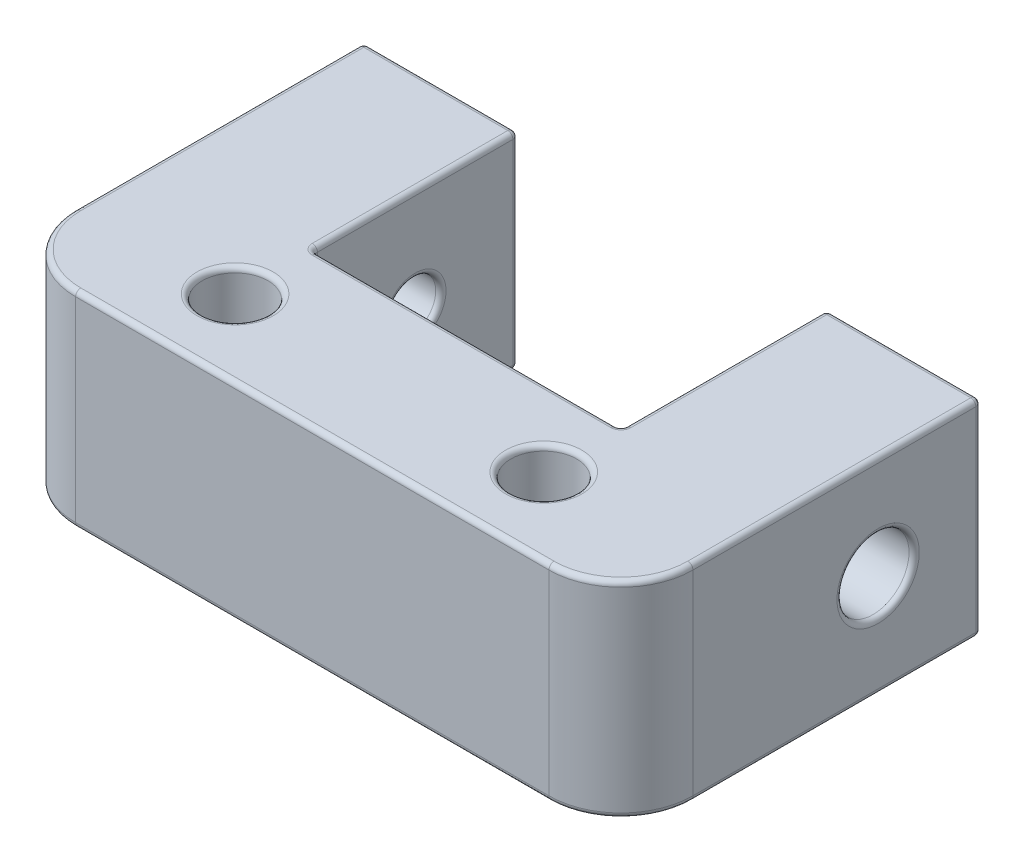
SolidWorks part; units mm, degrees
ref_plane "Front Plane" through (0, 0, 0) normal (0, 0, 1) x (1, 0, 0)
ref_plane "Top Plane" through (0, 0, 0) normal (0, 1, 0) x (1, 0, 0)
ref_plane "Right Plane" through (0, 0, 0) normal (1, 0, 0) x (0, 0, -1)
sketch "Sketch1" plane through (0, 0, 0) normal (0, 1, 0) x (1, 0, 0)
  line L1 (-30, -12.5) -> (30, -12.5)
  line L2 (-30, -12.5) -> (-30, 12.5)
  line L3 (-30, 12.5) -> (30, 12.5)
  line L4 (30, -12.5) -> (30, 12.5)
  line L5 (-30, -12.5) -> (30, 12.5) construction
  line L6 (-30, 12.5) -> (30, -12.5) construction
  line L9 (-15, -7.5) -> (15, -7.5)
  line L10 (-25, 7.5) -> (25, 7.5) construction
  line L11 (-25, -7.5) -> (-25, 7.5) construction
  line L12 (25, -7.5) -> (25, 7.5) construction
  line L13 (-30, -14) -> (30, -14) construction
  line L14 (-30, -12.5) -> (30, -12.5)
  line L15 (-30, -12.5) -> (-30, -15.5)
  line L16 (-23, -22.5) -> (23, -22.5)
  line L17 (30, -12.5) -> (30, -15.5)
  line L18 (-30, -22.5) -> (0, -22.5) construction
  line L19 (0, -22.5) -> (0, 12.5) construction
  line L20 (-15, 0) -> (15, 0) construction
  line L21 (-15, 12.5) -> (-15, -7.5)
  line L22 (15, 12.5) -> (15, -7.5)
  line L23 (-25, -7.5) -> (25, -7.5) construction
  circle A0 centre (-15, -15) radius 3.2
  circle A1 centre (15, -15) radius 3.2
  arc A2 (23, -22.5) -> (30, -15.5) centre (23, -15.5) ccw
  arc A3 (-30, -15.5) -> (-23, -22.5) centre (-23, -15.5) ccw
  point P0 (0, 0)
  point P19 (-15, -15)
  point P31 (0, 0)
  dimension "D5" = 6.4
  dimension "D6" = 7
  dimension "D1" = 25
  dimension "D2" = 60
  dimension "D4" = 10
extrude "Boss-Extrude1" add sketch "Sketch1" along normal blind 20 contours L9 L3 L2 L1 L4 | L15 A3 L16 A2 L17 L1 A1 A0 region at (-29.35, 0, 0) region at (0, 0, 17.6319)
sketch "Sketch2" plane through (-30, 0, 0) normal (-1, 0, 0) x (0, 0, 1)
  line L0 (-12.5, 10) -> (-2.5, 10) construction
  line L1 (-12.5, 20) -> (-12.5, 0) construction
  circle A0 centre (-2.5, 10) radius 2.5
  dimension "D2" = 5
  dimension "D1" = 10
extrude "Cut-Extrude1" cut sketch "Sketch2" against normal blind 70
fillet "Fillet1" radius 0.5 34 edges at (-15, 0, 18.2) (15, 0, 18.2) (-27.9497, 0, 20.4497) (0, 0, 22.5) (27.9497, 0, 20.4497) (0, 0, 7.5) (30, 0, 1.5) (30, 10, 0) (-22.5, 0, -12.5) (-30, 10, -12.5) (-30, 0, 1.5) (-30, 10, 0) (30, 10, -12.5) (22.5, 0, -12.5) (-15, 20, 18.2) (15, 20, 18.2) (22.5, 20, -12.5) (30, 20, 1.5) (27.9497, 20, 20.4497) (0, 20, 22.5) (-27.9497, 20, 20.4497) (-30, 20, 1.5) (-22.5, 20, -12.5) (0, 20, 7.5) (15, 10, 7.5) (-15, 10, 7.5) (15, 0, -2.5) (-15, 0, -2.5) (-15, 10, -12.5) (15, 10, -12.5) (-15, 20, -2.5) (15, 20, -2.5) (-15, 10, -5) (15, 10, -5)
sketch "Sketch3" plane through (-30, 0, 0) normal (-1, 0, 0) x (0, 0, 1)
  line L1 (2.6962, 10) -> (0.0981, 14.5)
  line L2 (0.0981, 14.5) -> (-5.0981, 14.5)
  line L3 (-5.0981, 14.5) -> (-7.6962, 10)
  line L4 (-7.6962, 10) -> (-5.0981, 5.5)
  line L5 (-5.0981, 5.5) -> (0.0981, 5.5)
  line L6 (0.0981, 5.5) -> (2.6962, 10)
  circle A0 centre (-2.5, 10) radius 4.5 construction
  dimension "D1" = 9
sketch "Sketch4" plane through (30, 0, 0) normal (1, 0, 0) x (0, 0, -1)
  circle A0 centre (2.5, 10) radius 3.5
  dimension "D1" = 7
extrude "Cut-Extrude2" cut sketch "Sketch4" against normal blind 10
extrude "Cut-Extrude3" cut sketch "Sketch3" against normal blind 10
fillet "Fillet2" radius 0.5 9 edges at (-30, 12.25, 1.3971) (-30, 14.5, -2.5) (-30, 12.25, -6.3971) (-30, 7.75, -6.3971) (-30, 5.5, -2.5) (-30, 7.75, 1.3971) (30, 10, -6) (20, 10, -5) (20, 10, -6)
